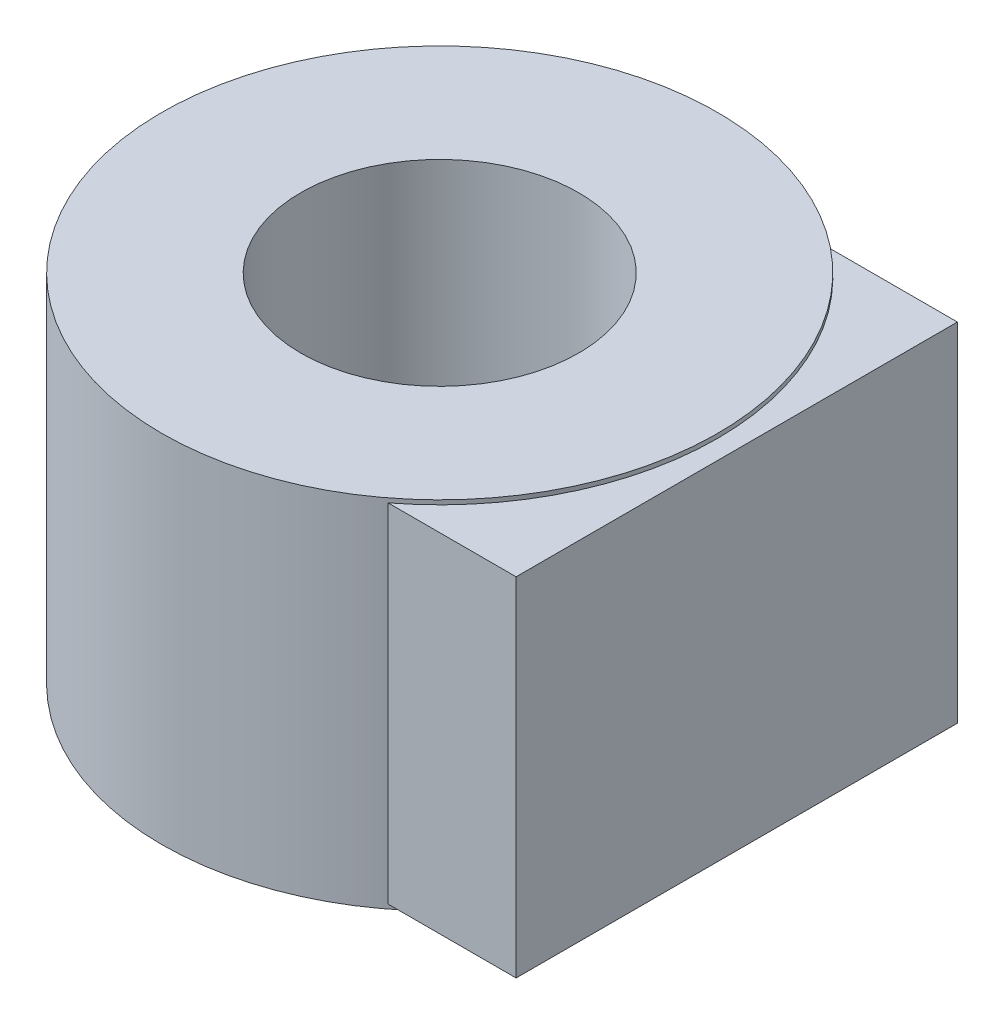
SolidWorks part; units mm, degrees
ref_plane "Front Plane" through (0, 0, 0) normal (0, 0, 1) x (1, 0, 0)
ref_plane "Top Plane" through (0, 0, 0) normal (0, 1, 0) x (1, 0, 0)
ref_plane "Right Plane" through (0, 0, 0) normal (1, 0, 0) x (0, 0, -1)
sketch "Sketch1" plane through (0, 0, 0) normal (0, 0, 1) x (1, 0, 0)
  line L1 (-18, -10) -> (18, -10)
  line L2 (-18, -10) -> (-18, 10)
  line L3 (-18, 10) -> (18, 10)
  line L4 (18, -10) -> (18, 10)
  line L5 (-18, -10) -> (18, 10) construction
  line L6 (-18, 10) -> (18, -10) construction
  point P0 (0, 0)
  dimension "D1" = 20
  dimension "D2" = 36
extrude "Boss-Extrude1" add sketch "Sketch1" along normal mid plane 25.4
sketch "Sketch2" plane through (0, 0, 0) normal (0, 1, 0) x (1, 0, 0)
  line L0 (-18, -12.7) -> (-18, 12.7) construction
  circle A0 centre (-18, 0) radius 16
  dimension "D1" = 32
extrude "Boss-Extrude2" add sketch "Sketch2" along normal mid plane 20.5
sketch "Sketch3" plane through (0, 10.25, 0) normal (0, 1, 0) x (1, 0, 0)
  line L0 (-18, 16) -> (-18, -16) construction
  line L1 (-34, 0) -> (-2, 0) construction
  circle A0 centre (-18, 0) radius 16 construction
  arc A1 (-8.2681, -12.7) -> (-8.2681, 12.7) centre (-18, 0) ccw construction
  circle A2 centre (-18, 0) radius 8
  dimension "D1" = 16
extrude "Cut-Extrude1" cut sketch "Sketch3" against normal blind 33
sketch "Sketch4" plane through (0, 10, 0) normal (0, 1, 0) x (1, 0, 0)
  line L0 (18, 12.7) -> (-8.2681, 12.7) construction
  line L1 (-0.902, 12.7) -> (-0.902, -12.7)
  line L2 (18, -12.7) -> (-8.2681, -12.7) construction
  line L3 (-0.902, -12.7) -> (18, -12.7)
  line L4 (18, -12.7) -> (18, 12.7)
  line L5 (18, -12.7) -> (18, 12.7) construction
  line L6 (18, 12.7) -> (-0.902, 12.7)
extrude "Cut-Extrude2" cut sketch "Sketch4" against normal through all
scale "Scale1" scale about centroid uniform scaling yes scale factor 0.7
scale "Scale2" scale about centroid uniform scaling yes scale factor 0.5
